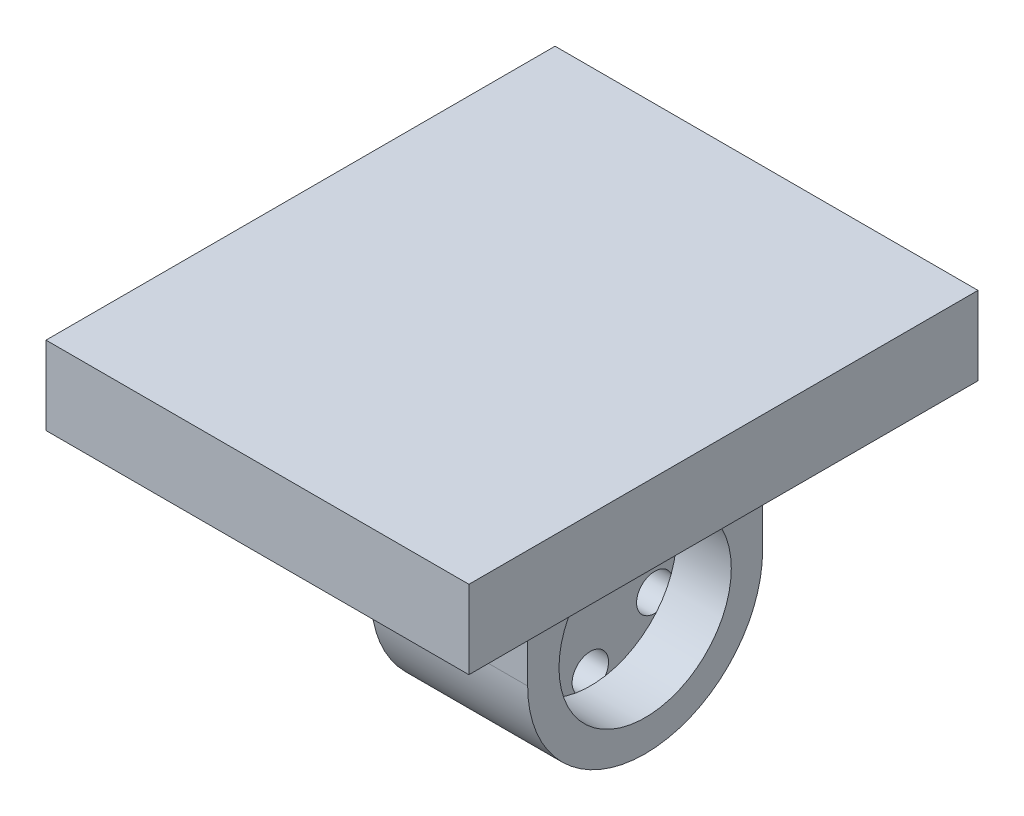
SolidWorks part; units mm, degrees
material "ABS PC"
ref_plane "Front Plane" through (0, 0, 0) normal (0, 0, 1) x (1, 0, 0)
ref_plane "Top Plane" through (0, 0, 0) normal (0, 1, 0) x (1, 0, 0)
ref_plane "Right Plane" through (0, 0, 0) normal (1, 0, 0) x (0, 0, -1)
sketch "Sketch1" plane through (0, 0, 0) normal (0, 1, 0) x (1, 0, 0)
  line L1 (-27, -32.5) -> (27, -32.5)
  line L2 (-27, -32.5) -> (-27, 32.5)
  line L3 (-27, 32.5) -> (27, 32.5)
  line L4 (27, -32.5) -> (27, 32.5)
  line L5 (-27, -32.5) -> (27, 32.5) construction
  line L6 (-27, 32.5) -> (27, -32.5) construction
  point P0 (0, 0)
  dimension "D1" = 54
  dimension "D2" = 65
extrude "Boss-Extrude1" add sketch "Sketch1" along normal blind 10
sketch "Sketch2" plane through (0, 0, 0) normal (0, -1, 0) x (1, 0, 0)
  line L0 (-3, 15) -> (-3, -15)
  line L1 (-3, 15) -> (17, 15)
  line L2 (27, 32.5) -> (27, -32.5) construction
  line L3 (-3, -15) -> (17, -15)
  line L4 (17, 15) -> (17, -15)
  point P0 (-3, 0)
  dimension "D1" = 10
  dimension "D2" = 20
  dimension "D3" = 30
extrude "Boss-Extrude2" add sketch "Sketch2" along normal blind 30
fillet "Fillet1" radius 15 2 edges at (7, -30, -15) (7, -30, 15)
sketch "Sketch3" plane through (17, 0, 0) normal (1, 0, 0) x (0, 0, -1)
  circle A0 centre (0, -15) radius 11
  dimension "D1" = 22
extrude "Cut-Extrude1" cut sketch "Sketch3" against normal blind 7
sketch "Sketch4" plane through (-3, 0, 0) normal (-1, 0, 0) x (0, 0, 1)
  circle A0 centre (0, -15) radius 6
  dimension "D1" = 12
extrude "Cut-Extrude2" cut sketch "Sketch4" against normal blind 5
sketch "Sketch5" plane through (-3, 0, 0) normal (-1, 0, 0) x (0, 0, 1)
  circle A0 centre (0, -15) radius 9.5 construction
  circle A1 centre (0, -5.5) radius 1.5875
  circle A2 centre (8.2272, -10.25) radius 1.5875
  circle A3 centre (8.2272, -19.75) radius 1.5875
  circle A4 centre (0, -24.5) radius 1.5875
  circle A5 centre (-8.2272, -19.75) radius 1.5875
  circle A6 centre (-8.2272, -10.25) radius 1.5875
  point P18 (0, -15)
  dimension "D1" = 19
  dimension "D2" = 3.175
  dimension "D3" = 6
extrude "Cut-Extrude3" cut sketch "Sketch5" against normal blind 7
sketch "Sketch6" plane through (10, 0, 0) normal (1, 0, 0) x (0, 0, -1)
  circle A0 centre (0, -5.5) radius 1.5875 construction
  circle A1 centre (0, -15) radius 11
  circle A2 centre (0, -15) radius 11 construction
  circle A3 centre (0, -5.5) radius 1.5875 construction
  circle A4 centre (0, -5.5) radius 2.3241
  circle A5 centre (8.2272, -10.25) radius 2.3241
  circle A6 centre (8.2272, -19.75) radius 2.3241
  circle A7 centre (0, -24.5) radius 2.3241
  circle A8 centre (-8.2272, -19.75) radius 2.3241
  circle A9 centre (-8.2272, -10.25) radius 2.3241
  point P20 (0, -15)
  dimension "D2" = 4.6482
  dimension "D1" = 0
  dimension "D3" = 6
extrude "Cut-Extrude4" cut sketch "Sketch6" against normal blind 6
